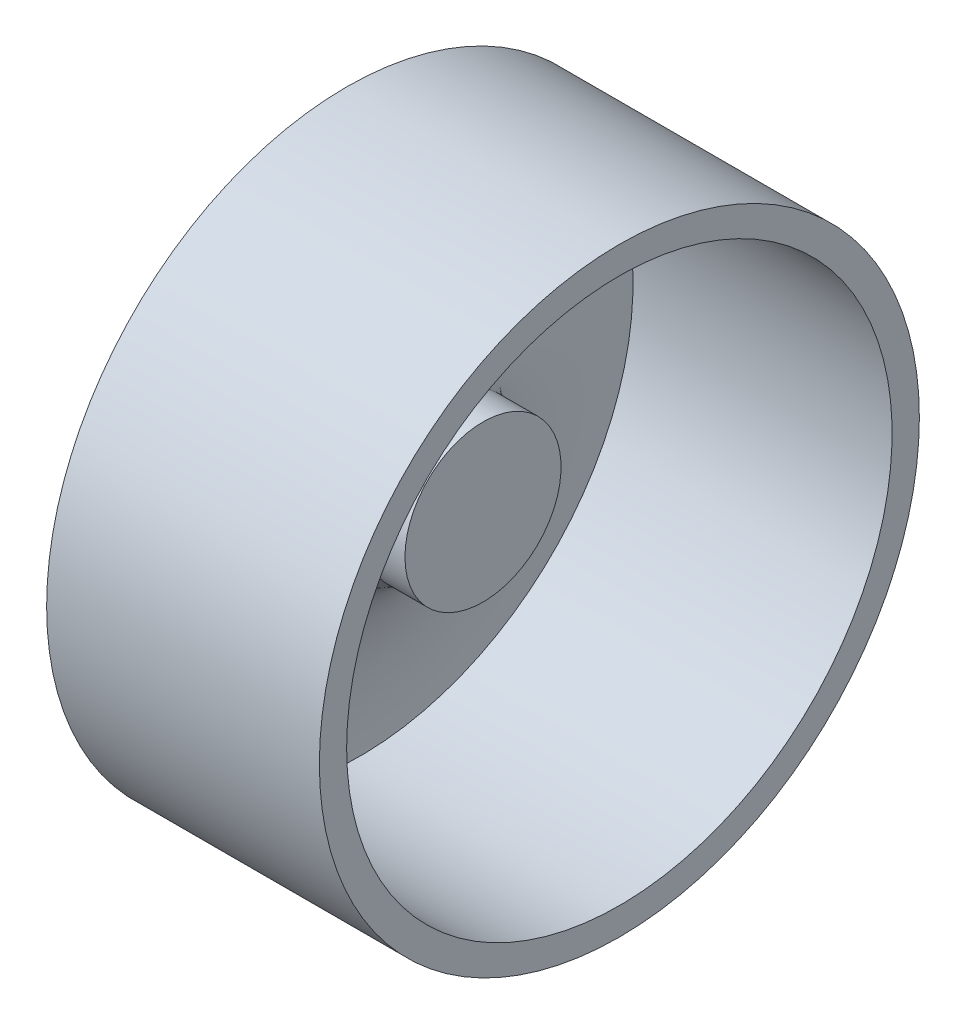
SolidWorks part; units mm, degrees
ref_plane "Front Plane" through (0, 0, 0) normal (0, 0, 1) x (1, 0, 0)
ref_plane "Top Plane" through (0, 0, 0) normal (0, 1, 0) x (1, 0, 0)
ref_plane "Right Plane" through (0, 0, 0) normal (1, 0, 0) x (0, 0, -1)
sketch "Reference" plane through (0, 0, 0) normal (0, 1, 0) x (1, 0, 0)
  line L0 (0, 25.4) -> (0, 0) construction
  line L5 (-12.7, -27.94) -> (12.7, -27.94) construction
  line L6 (-12.7, -27.94) -> (-12.7, 27.94) construction
  line L7 (-12.7, 27.94) -> (12.7, 27.94) construction
  line L8 (12.7, 25.4) -> (12.7, 27.94) construction
  line L9 (-12.7, -27.94) -> (12.7, 27.94) construction
  line L10 (-12.7, 27.94) -> (12.7, -27.94) construction
  line L11 (-12.7, 27.94) -> (12.7, 27.94) construction
  line L12 (-12.7, 25.4) -> (12.7, 25.4) construction
  line L13 (-3.81, 6) -> (-3.81, -6) construction
  line L14 (-3.81, 6) -> (0, 6) construction
  line L15 (-12.7, 25.4) -> (12.7, 25.4) construction
  line L16 (-3.81, 7.27) -> (0, 7.27) construction
  line L17 (-4.318, 6.0894) -> (-4.318, 0) construction
  spline S0 degree 2 poles (-12.7, 25.4) (-13.6864, 4.2682) (0, 6) knots 0 0 0 1 1 1 construction
  spline S1 degree 2 poles (-3.81, 7.27) (-11.423, 8.519) (-11.43, 25.4) knots 0 0 0 1 1 1 construction
  point P0 (0, 0)
  point P15 (-3.81, 0)
  dimension "D8" = 0.508
  dimension "D1" = 25.4
  dimension "D2" = 55.88
  dimension "D3" = 2.54
  dimension "D4" = 12
  dimension "D5" = 3.81
  dimension "D6" = 1.27
  dimension "D7" = 1.27
sketch "Sketch2" plane through (0, 0, 0) normal (0, 1, 0) x (1, 0, 0)
  line L0 (-3.81, 0) -> (0, 0)
  line L1 (-3.81, 6) -> (-3.81, -6) construction
  line L2 (0, 0) -> (0, 6)
  line L3 (0, 6) -> (0, 7.27)
  line L4 (0, 7.27) -> (-3.81, 7.27)
  line L5 (-4.318, 6.0894) -> (-4.318, 0)
  line L6 (-4.318, 0) -> (-3.81, 0)
  line L7 (-12.7, 25.4) -> (-12.7, 27.94)
  line L8 (-12.7, 27.94) -> (12.7, 27.94)
  line L9 (12.7, 27.94) -> (12.7, 25.4)
  line L11 (-11.43, 25.4) -> (12.7, 25.4)
  spline S0 degree 2 poles (-4.318, 6.0894) (-12.8591, 7.3367) (-12.7, 25.4) knots 0 0 0 1 1 1
  spline S1 degree 3 poles (-11.43, 25.4) (-11.6399, 16.186) (-9.5776, 8.523) (-3.81, 7.27) knots 0 0 0 0 1 1 1 1
revolve "Main Revolve" add sketch "Sketch2" angle 360 about L0
